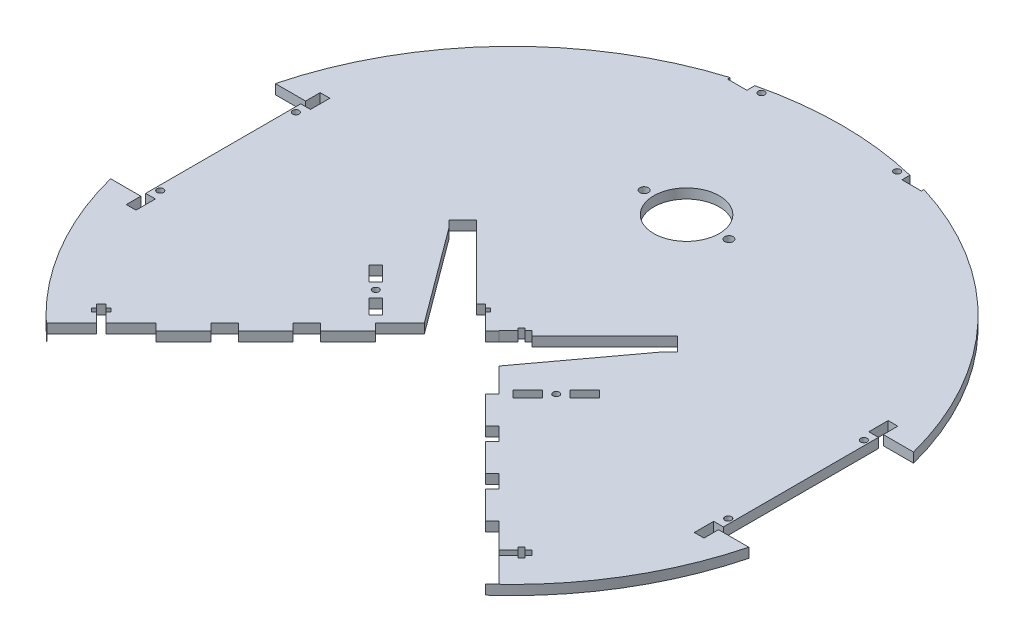
SolidWorks part; units mm, degrees
ref_plane "Front Plane" through (0, 0, 0) normal (0, 0, 1) x (1, 0, 0)
ref_plane "Top Plane" through (0, 0, 0) normal (0, 1, 0) x (1, 0, 0)
ref_plane "Right Plane" through (0, 0, 0) normal (1, 0, 0) x (0, 0, -1)
sketch "Sketch1" plane through (0, 0, 0) normal (0, 1, 0) x (1, 0, 0)
  circle A0 centre (0, 0) radius 215.9
  dimension "D1" = 431.8
extrude "Base Plate" add sketch "Sketch1" along normal blind 6.35
sketch "Sketch2" plane through (0, 6.35, 0) normal (0, 1, 0) x (1, 0, 0)
  line L0 (0, -17.4608) -> (-143.6841, -161.1449)
  line L1 (0, -36.2008) -> (0, -54.9716) construction
  line L2 (0, -17.4608) -> (143.6841, -161.1449)
  circle A0 centre (0, 0) radius 215.9 construction
  arc A1 (-143.6841, -161.1449) -> (143.6841, -161.1449) centre (0, 0) ccw
  dimension "D1" = 203.2
  dimension "D2" = 45
extrude "V Funnel Cut" cut sketch "Sketch2" against normal through all
sketch "Sketch4" plane through (0, 6.35, 0) normal (0, 1, 0) x (1, 0, 0)
  line L0 (0, 54.2551) -> (0, 121.7464) construction
  line L1 (-213.36, 53.975) -> (-191.77, 53.975)
  line L2 (-215.9, 51.435) -> (-215.9, -51.435)
  line L3 (-213.36, -53.975) -> (-191.77, -53.975)
  line L4 (-189.23, 51.435) -> (-189.23, -51.435)
  line L5 (-17.8666, 0) -> (24.1783, 0) construction
  line L6 (-215.9, -69.5481) -> (-215.9, -224.3367) construction
  line L8 (-215.9, 53.975) -> (-189.23, 53.975)
  line L9 (-215.9, 53.975) -> (-215.9, -53.975)
  line L10 (-215.9, -53.975) -> (-189.23, -53.975)
  line L11 (-189.23, 53.975) -> (-189.23, -53.975)
  arc A0 (-213.36, -53.975) -> (-215.9, -51.435) centre (-213.36, -51.435) cw
  arc A1 (-191.77, -53.975) -> (-189.23, -51.435) centre (-191.77, -51.435) ccw
  arc A2 (-189.23, 51.435) -> (-191.77, 53.975) centre (-191.77, 51.435) ccw
  arc A3 (-213.36, 53.975) -> (-215.9, 51.435) centre (-213.36, 51.435) ccw
  arc A4 (143.6841, -161.1449) -> (-143.6841, -161.1449) centre (0, 0) ccw construction
  arc M13 (143.6841, -161.1449) -> (-143.6841, -161.1449) centre (0, 0) ccw
  dimension "D5" = 2.54
  dimension "D4" = 2.54
  dimension "D1" = 26.67
  dimension "D3" = 107.95
extrude "Wheel Hole Slot" cut sketch "Sketch4" against normal through all contours A3 L8 L9 | L1 A3 L2 M13 | L4 A2 L1 L3 A1 M13 | A2 L11 L8 | A0 L3 L2 M13 | L10 A0 L9 | A1 L10 L11 region at (-215.3326, 6.35, -53.4076) region at (-213.8321, 6.35, -40.3773) region at (-201.5273, 6.35, 0) region at (-189.7974, 6.35, -53.4076) region at (-213.8321, 6.35, 40.3773) region at (-215.3326, 6.35, 53.4076) region at (-189.7974, 6.35, 53.4076)
mirror "Wheel Slot Mirror" about plane through (0, 0, 0) normal (1, 0, 0) of "Wheel Hole Slot"
sketch "Sketch6" plane through (0, 6.35, 0) normal (0, 1, 0) x (1, 0, 0)
  line L0 (-35.921, -53.3819) -> (-29.5658, -59.7371) construction
  line L1 (0, -17.4608) -> (-143.6841, -161.1449) construction
  line L2 (143.6841, -161.1449) -> (0, -17.4608) construction
  line B0 (-61.3685, -23.4443) -> (-71.1005, -13.7123)
  line B1 (-61.3685, -23.4443) -> (-65.8586, -27.9344)
  line B2 (-71.1005, -13.7123) -> (-75.5906, -18.2024)
  line B3 (-65.8586, -27.9344) -> (-75.5906, -18.2024)
  line B4 (-52.3882, -32.4245) -> (-42.6562, -42.1565)
  line B5 (-56.8783, -36.9147) -> (-47.1463, -46.6467)
  line B6 (-42.6562, -42.1565) -> (-47.1463, -46.6467)
  line B7 (-52.3882, -32.4245) -> (-56.8783, -36.9147)
  circle B8 centre (-59.1234, -30.1795) radius 2.0955
  dimension "D1" = 50.8
  dimension "D2" = 12.7
sketch_block_instance "BoltTab-1"
sketch_block "BoltTab" parameters "D1"=4.191, "D2"=6.35, "D3"=6.35
extrude "Arm Post Connector" cut sketch "Sketch6" against normal through all
mirror "Arm Post Connector Mirror" about plane through (0, 0, 0) normal (1, 0, 0) of "Arm Post Connector"
sketch "Sketch8" plane through (0, 0, 0) normal (0, -1, 0) x (1, 0, 0)
  line L0 (-189.23, -63.5) -> (-189.23, -50.8) construction
  line L1 (-189.23, -63.5) -> (-182.88, -63.5) construction
  line L2 (-182.88, -63.5) -> (-182.88, -50.8) construction
  line L3 (-189.23, -50.8) -> (-182.88, -50.8) construction
  line L4 (-189.23, -63.5) -> (-189.23, -50.8)
  line L5 (-189.23, -63.5) -> (-182.88, -63.5)
  line L6 (-182.88, -63.5) -> (-182.88, -50.8)
  line L7 (-189.23, -50.8) -> (-182.88, -50.8)
  line L8 (-189.23, 50.8) -> (-182.88, 50.8) construction
  line L9 (-189.23, 63.5) -> (-189.23, 50.8) construction
  line L10 (-182.88, 63.5) -> (-182.88, 50.8) construction
  line L11 (-189.23, 63.5) -> (-182.88, 63.5) construction
  line L12 (-189.23, 50.8) -> (-182.88, 50.8)
  line L13 (-189.23, 63.5) -> (-189.23, 50.8)
  line L14 (-182.88, 63.5) -> (-182.88, 50.8)
  line L15 (-189.23, 63.5) -> (-182.88, 63.5)
  line L16 (-189.23, -46.5836) -> (-182.88, -46.5836) construction
  line L17 (-189.23, -42.3164) -> (-182.88, -42.3164) construction
  line L18 (-189.23, -46.5836) -> (-182.88, -46.5836) construction
  line L19 (-189.23, -42.3164) -> (-182.88, -42.3164) construction
  line L20 (-186.055, -42.3164) -> (-186.055, -46.5836) construction
  line L21 (-189.23, 42.3164) -> (-182.88, 42.3164) construction
  line L22 (-189.23, 46.5836) -> (-182.88, 46.5836) construction
  line L23 (-189.23, 42.3164) -> (-182.88, 42.3164) construction
  line L24 (-189.23, 46.5836) -> (-182.88, 46.5836) construction
  line L25 (-186.055, 42.3164) -> (-186.055, 46.5836) construction
  circle A0 centre (-186.055, -44.45) radius 2.1336
  circle A1 centre (-186.055, 44.45) radius 2.1336
extrude "Motor Mount Connector" cut sketch "Sketch8" against normal through all
mirror "Motor Mount Connector Mirror" about plane through (0, 0, 0) normal (1, 0, 0) of "Motor Mount Connector"
sketch "Sketch9" plane through (0, 0, 0) normal (0, -1, 0) x (1, 0, 0)
  line L0 (-63.5, -204.6423) -> (-63.5, -210.9923) construction
  line L1 (-63.5, -204.6423) -> (-50.8, -204.6423) construction
  line L2 (-50.8, -204.6423) -> (-50.8, -210.9923) construction
  line L3 (-63.5, -210.9923) -> (-50.8, -210.9923) construction
  line L4 (-63.5, -204.6423) -> (-63.5, -210.9923)
  line L5 (-63.5, -204.6423) -> (-50.8, -204.6423)
  line L6 (-50.8, -204.6423) -> (-50.8, -210.9923)
  line L7 (-63.5, -210.9923) -> (-50.8, -210.9923)
  line L8 (-46.5836, -204.6423) -> (-46.5836, -210.9923) construction
  line L9 (-42.3164, -204.6423) -> (-42.3164, -210.9923) construction
  line L10 (-46.5836, -204.6423) -> (-46.5836, -210.9923) construction
  line L11 (-42.3164, -204.6423) -> (-42.3164, -210.9923) construction
  line L12 (-46.5836, -207.8173) -> (-42.3164, -207.8173) construction
  line L13 (42.3164, -204.6423) -> (42.3164, -210.9923) construction
  line L14 (46.5836, -204.6423) -> (46.5836, -210.9923) construction
  line L15 (42.3164, -204.6423) -> (42.3164, -210.9923) construction
  line L16 (46.5836, -204.6423) -> (46.5836, -210.9923) construction
  line L17 (50.8, -210.9923) -> (63.5, -210.9923)
  line L18 (63.5, -210.9923) -> (63.5, -204.6423)
  line L19 (63.5, -204.6423) -> (50.8, -204.6423)
  line L20 (50.8, -204.6423) -> (50.8, -210.9923)
  line L21 (50.8, -210.9923) -> (63.5, -210.9923)
  line L22 (63.5, -210.9923) -> (63.5, -204.6423)
  line L23 (63.5, -204.6423) -> (50.8, -204.6423)
  line L24 (50.8, -204.6423) -> (50.8, -210.9923)
  line L25 (42.3164, -207.8173) -> (46.5836, -207.8173) construction
  circle A0 centre (-44.45, -207.8173) radius 2.1336
  circle A1 centre (44.45, -207.8173) radius 2.1336
  dimension "D1" = 0
extrude "Back Mount Connector" cut sketch "Sketch9" against normal through all
sketch "Sketch11" plane through (0, 6.35, 0) normal (0, 1, 0) x (1, 0, 0)
  line L0 (0, 61.4305) -> (0, 100.7164) construction
  line L1 (-82.8279, 215.9) -> (68.7629, 215.9) construction
  line L2 (-27.7813, 114.3) -> (27.7813, 114.3) construction
  circle A0 centre (0, 114.3) radius 21.463
  circle A4 centre (27.7813, 114.3) radius 2.7781
  circle A5 centre (-27.7813, 114.3) radius 2.7781
  arc A6 (209.0443, 53.975) -> (63.5, 206.3506) centre (0, 0) ccw construction
  dimension "D1" = 42.926
  dimension "D3" = 5.5563
  dimension "D2" = 101.6
  dimension "D4" = 27.7813
sketch "Sketch16" plane through (0, 6.35, 0) normal (0, 1, 0) x (1, 0, 0)
  line L0 (20.6696, -38.1304) -> (70.3145, 28.968)
  line L1 (143.6841, -161.1449) -> (0, -17.4608) construction
  line L3 (20.6696, -38.1304) -> (25.1597, -33.6403) construction
  line L4 (63.0858, 36.1967) -> (4.7141, -22.1749)
  line L5 (0, 0) -> (0, 51.8981) construction
  line L6 (70.3145, 28.968) -> (63.0858, 36.1967)
  line L7 (20.6696, -38.1304) -> (4.7141, -22.1749)
  line L8 (-70.3145, 28.968) -> (-63.0858, 36.1967)
  line L9 (-63.0858, 36.1967) -> (-4.7141, -22.1749)
  line L10 (-20.6696, -38.1304) -> (-70.3145, 28.968)
  line L11 (-20.6696, -38.1304) -> (-4.7141, -22.1749)
  dimension "D1" = 82.55
extrude "Cut-Extrude2" cut sketch "Sketch16" against normal through all
extrude "Caster Wheel Hole" cut sketch "Sketch11" against normal through all
sketch "Sketch12" plane through (8.7304, 0, 8.7304) normal (0.7071, 0, 0.7071) x (0.7071, 0, -0.7071)
  line L0 (-164.8817, 6.35) -> (-164.8817, 0) construction
  line L1 (-215.5467, 6.35) -> (-164.8817, 6.35)
  line L2 (-215.5467, 6.35) -> (-215.5467, 0)
  line L3 (-215.5467, 0) -> (-164.8817, 0)
  line L4 (-164.8817, 6.35) -> (-164.8817, 0)
  line L5 (-12.3467, 0) -> (-19.0134, 0) construction
  line L6 (-12.3467, 6.35) -> (-19.0134, 6.35) construction
  line L7 (-139.4817, 6.35) -> (-126.7817, 6.35)
  line L8 (-139.4817, 6.35) -> (-139.4817, 0)
  line L9 (-139.4817, 0) -> (-126.7817, 0)
  line L10 (-126.7817, 6.35) -> (-126.7817, 0)
  line L11 (-139.4817, 0) -> (-139.4817, 6.35) construction
  line L12 (-126.7817, 6.35) -> (-126.7817, 0) construction
  line L13 (-101.3817, 0) -> (-101.3817, 6.35) construction
  line L14 (-101.3817, 6.35) -> (-88.6817, 6.35)
  line L15 (-101.3817, 6.35) -> (-101.3817, 0)
  line L16 (-101.3817, 0) -> (-88.6817, 0)
  line L17 (-88.6817, 6.35) -> (-88.6817, 0)
  line L18 (-88.6817, 6.35) -> (-88.6817, 0) construction
  line L19 (-63.2817, 0) -> (-63.2817, 6.35) construction
  line L20 (-63.2817, 6.35) -> (-12.3467, 6.35)
  line L21 (-63.2817, 6.35) -> (-63.2817, 0)
  line L22 (-63.2817, 0) -> (-12.3467, 0)
  line L23 (-12.3467, 6.35) -> (-12.3467, 0)
extrude "V Funnel Tabs" cut sketch "Sketch12" against normal blind 6.35
mirror "V Funnel Tab Mirror" about plane through (0, 0, 0) normal (1, 0, 0) of "V Funnel Tabs"
sketch "Sketch13" plane through (0, 6.35, 0) normal (0, 1, 0) x (1, 0, 0)
  line L0 (-2.9589, -20.4197) -> (-11.9392, -29.4)
  line L1 (-2.9589, -20.4197) -> (-65.8207, 42.4421)
  line L2 (-11.9392, -29.4) -> (-74.801, 33.4618)
  line L3 (-65.8207, 42.4421) -> (-74.801, 33.4618)
  line L4 (-40.5066, -48.9872) -> (-36.0165, -53.4773) construction
  line L8 (-36.0165, -53.4773) -> (-53.977, -71.4378) construction
  line L10 (55.6675, -88.0264) -> (50.4158, -82.7747) construction
  line L11 (-137795.0233, 137762.6644) -> (172087.8094, -172120.1683) construction
  dimension "D1" = 88.9
  dimension "D2" = 12.7
extrude "Peg Clearance" cut sketch "Sketch13" against normal through all
mirror "Peg Clearance Mirror" about plane through (0, 0, 0) normal (1, 0, 0) of "Peg Clearance"
sketch "Sketch14" plane through (0, 6.35, 0) normal (0, 1, 0) x (1, 0, 0)
  line L0 (-34.9905, 14.5708) -> (1.5967, -22.0164) construction
  line L1 (-16.1795, -24.66) -> (-4.4901, -12.9707) construction
  line L3 (0, -17.4608) -> (-4.4901, -12.9707) construction
  line L4 (-7.449, -15.9296) -> (-65.8207, 42.4421) construction
  line B0 (-7.4783, -15.9588) -> (-4.4609, -12.9415)
  line B1 (-12.9023, -4.5) -> (-11.2679, -2.8656)
  line B2 (-11.2679, -2.8656) -> (-9.0229, -5.1107)
  line B3 (-9.0229, -5.1107) -> (-10.6573, -6.7451)
  line B4 (-10.6573, -6.7451) -> (-4.4609, -12.9415)
  line B5 (-12.9023, -4.5) -> (-15.2372, -2.1652)
  line B6 (-15.2372, -2.1652) -> (-18.2546, -5.1825)
  line B7 (-15.9197, -7.5174) -> (-18.2546, -5.1825)
  line B8 (-13.6746, -9.7625) -> (-7.4783, -15.9588)
  line B9 (-15.309, -11.3969) -> (-13.6746, -9.7625)
  line B10 (-17.5541, -9.1518) -> (-15.309, -11.3969)
  line B11 (-15.9197, -7.5174) -> (-17.5541, -9.1518)
sketch_block_instance "TSlot-1"
sketch_block "TSlot" parameters "D1"=3.302, "D2"=3.175
extrude "V Funnel T Slot 1" cut sketch "Sketch14" against normal through all
sketch "Sketch15" plane through (0, 6.35, 0) normal (0, 1, 0) x (1, 0, 0)
  line L0 (-105.2335, -163.9609) -> (-173.0729, -96.1215) construction
  line L1 (-112.3487, -120.8293) -> (-107.8585, -125.3194) construction
  line L2 (-143.875, -161.3359) -> (-148.3652, -156.8457) construction
  line L3 (-108.5651, -117.0457) -> (-77.9363, -86.4169) construction
  line B0 (-131.8656, -140.3462) -> (-128.8482, -137.3288)
  line B1 (-137.2897, -128.8874) -> (-135.6553, -127.253)
  line B2 (-135.6553, -127.253) -> (-133.4102, -129.498)
  line B3 (-133.4102, -129.498) -> (-135.0446, -131.1324)
  line B4 (-135.0446, -131.1324) -> (-128.8482, -137.3288)
  line B5 (-137.2897, -128.8874) -> (-139.6245, -126.5525)
  line B6 (-139.6245, -126.5525) -> (-142.6419, -129.5699)
  line B7 (-140.307, -131.9047) -> (-142.6419, -129.5699)
  line B8 (-138.062, -134.1498) -> (-131.8656, -140.3462)
  line B9 (-139.6964, -135.7842) -> (-138.062, -134.1498)
  line B10 (-141.9414, -133.5391) -> (-139.6964, -135.7842)
  line B11 (-140.307, -131.9047) -> (-141.9414, -133.5391)
sketch_block_instance "TSlot-3"
extrude "V Funnel T Slot 2" cut sketch "Sketch15" against normal through all
mirror "Mirror1" about plane through (0, 0, 0) normal (1, 0, 0) of "V Funnel T Slot 2", "V Funnel T Slot 1"
